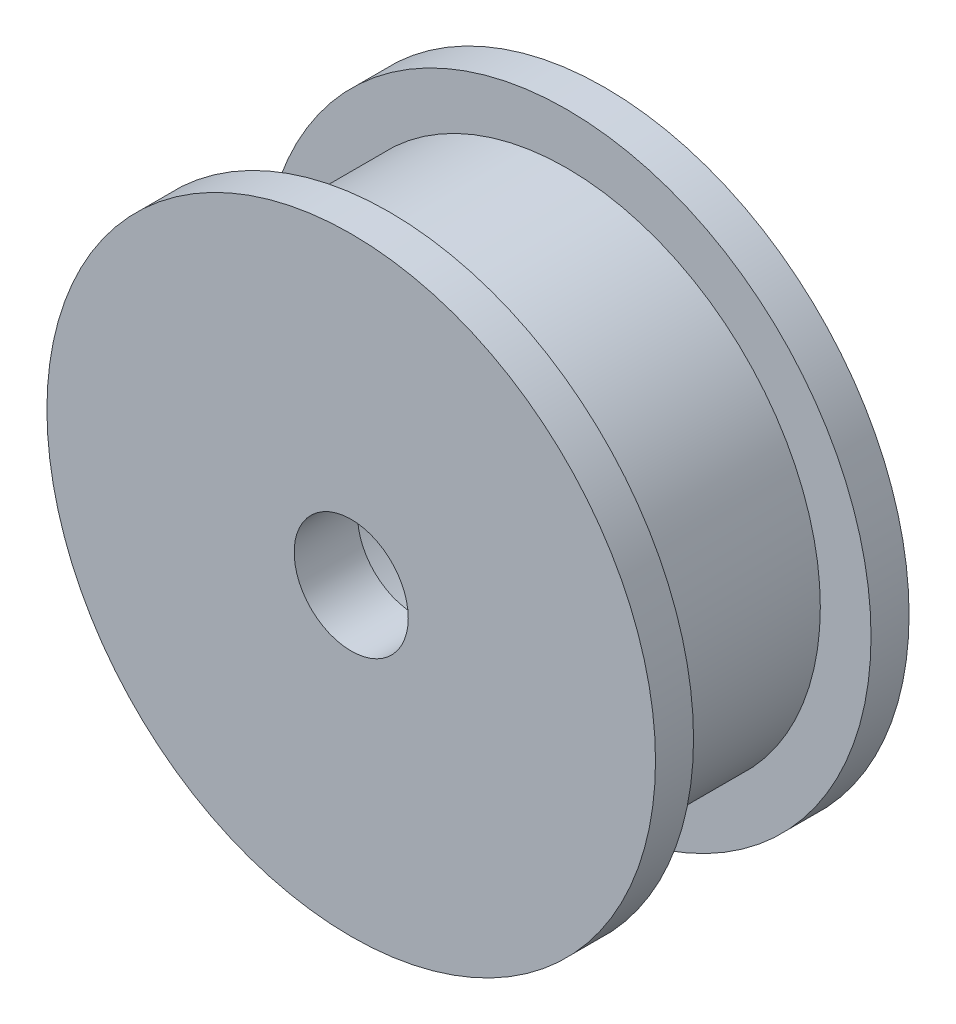
SolidWorks part; units mm, degrees
ref_plane "Front Plane" through (0, 0, 0) normal (0, 0, 1) x (1, 0, 0)
ref_plane "Top Plane" through (0, 0, 0) normal (0, 1, 0) x (1, 0, 0)
ref_plane "Right Plane" through (0, 0, 0) normal (1, 0, 0) x (0, 0, -1)
sketch "Sketch1" plane through (0, 0, 0) normal (0, 0, 1) x (1, 0, 0)
  circle A0 centre (0, 0) radius 10
  dimension "D1" = 20
extrude "Boss-Extrude1" add sketch "Sketch1" along normal blind 7
sketch "Sketch2" plane through (0, 0, 7) normal (0, 0, 1) x (1, 0, 0)
  circle A0 centre (0, 0) radius 12
  dimension "D1" = 24
extrude "Boss-Extrude2" add sketch "Sketch2" along normal blind 1.5
sketch "Sketch3" plane through (0, 0, 0) normal (0, 0, -1) x (-1, 0, 0)
  circle A0 centre (0, 0) radius 12
extrude "Boss-Extrude3" add sketch "Sketch3" along normal blind 1.5
sketch "Sketch4" plane through (0, 0, 8.5) normal (0, 0, 1) x (1, 0, 0)
  circle A0 centre (0, 0) radius 6.5
  dimension "D1" = 13
extrude "Cut-Extrude1" cut sketch "Sketch4" against normal through all
sketch "Sketch5" plane through (0, 0, 8.5) normal (0, 0, 1) x (1, 0, 0)
  circle A0 centre (0, 0) radius 6.5
  circle A1 centre (0, 0) radius 2.25
  dimension "D1" = 4.5
extrude "Boss-Extrude4" add sketch "Sketch5" against normal blind 2.5
